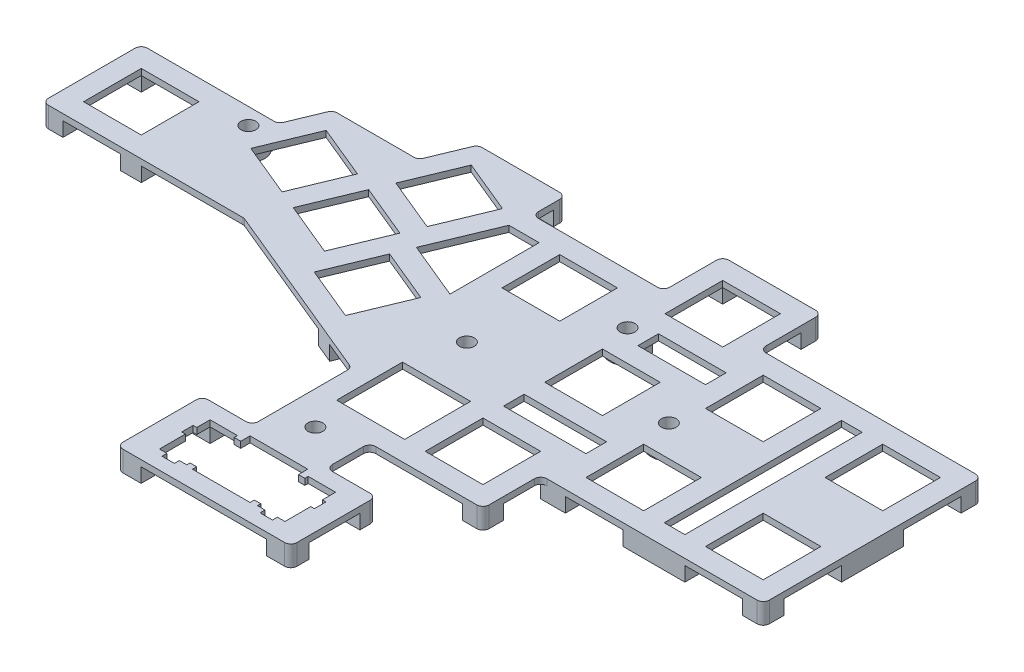
SolidWorks part; units mm, degrees
ref_plane "Front Plane" through (0, 0, 0) normal (0, 0, 1) x (1, 0, 0)
ref_plane "Top Plane" through (0, 0, 0) normal (0, 1, 0) x (1, 0, 0)
ref_plane "Right Plane" through (0, 0, 0) normal (1, 0, 0) x (0, 0, -1)
sketch "Button Reference" plane through (0, 0, 0) normal (0, 1, 0) x (1, 0, 0)
  line L0 (24.5, 61) -> (24.5, 32) construction
  line L1 (-36.2591, 48.1292) -> (-29.3708, 64.7591) construction
  line L2 (49.5, 75) -> (49.5, 46) construction
  line L3 (78.5, 75) -> (78.5, 46) construction
  line L4 (17.5, 0) -> (-17.5, 0) construction
  line L5 (-36.2591, 48.1292) -> (-19.6292, 41.2409) construction
  line L6 (17.5, -12.5) -> (-17.5, -12.5)
  line L7 (17.5, 12.5) -> (-17.5, 12.5)
  line L8 (24.6803, 89.9994) -> (49.5, 75) construction
  line L9 (24.6803, 89.9994) -> (24.5, 61) construction
  line L10 (-0.5241, 75.6559) -> (24.6803, 89.9994) construction
  line L11 (-0.5241, 75.6559) -> (24.5, 61) construction
  line L12 (-29.3708, 64.7591) -> (-12.7409, 57.8708) construction
  line L13 (-19.6292, 41.2409) -> (-12.7409, 57.8708) construction
  line L14 (-36.2591, 48.1292) -> (-12.7409, 57.8708) construction
  line L15 (-29.3708, 64.7591) -> (-19.6292, 41.2409) construction
  line L16 (-35.6984, 52.2266) -> (-28.8101, 68.8564) construction
  line L17 (-35.6984, 52.2266) -> (-52.3282, 59.1149) construction
  line L18 (-28.8101, 68.8564) -> (-45.4399, 75.7447) construction
  line L19 (-52.3282, 59.1149) -> (-45.4399, 75.7447) construction
  line L20 (-35.6984, 52.2266) -> (-45.4399, 75.7447) construction
  line L21 (-28.8101, 68.8564) -> (-52.3282, 59.1149) construction
  line L22 (-69.9281, 66.405) -> (-63.0398, 83.0348) construction
  line L23 (-69.9281, 66.405) -> (-53.2983, 59.5167) construction
  line L24 (-63.0398, 83.0348) -> (-46.41, 76.1465) construction
  line L25 (-53.2983, 59.5167) -> (-46.41, 76.1465) construction
  line L26 (-69.9281, 66.405) -> (-46.41, 76.1465) construction
  line L27 (-63.0398, 83.0348) -> (-53.2983, 59.5167) construction
  line L28 (-40.5692, 63.9856) -> (-22.9693, 56.6955) construction
  line L29 (-40.5692, 63.9856) -> (-58.1691, 71.2758) construction
  line L30 (-45.0381, 76.7148) -> (-38.1498, 93.3446) construction
  line L31 (-45.0381, 76.7148) -> (-28.4083, 69.8265) construction
  line L32 (-38.1498, 93.3446) -> (-21.52, 86.4563) construction
  line L33 (-28.4083, 69.8265) -> (-21.52, 86.4563) construction
  line L34 (-45.0381, 76.7148) -> (-21.52, 86.4563) construction
  line L35 (-38.1498, 93.3446) -> (-28.4083, 69.8265) construction
  line L36 (-40.5692, 63.9856) -> (-33.2791, 81.5855) construction
  line L37 (-24.5, 53) -> (-22.9693, 56.6955) construction
  line L38 (-58.1691, 71.2758) -> (-65.4592, 53.6759) construction
  line L39 (-65.4592, 53.6759) -> (-90.4039, 64.0083) construction
  line L40 (-70.5814, 66.1344) -> (-63.3104, 83.6881)
  line L41 (-63.3104, 83.6881) -> (-45.7105, 76.398)
  line L42 (-45.7105, 76.398) -> (-38.4204, 93.9979)
  line L43 (-38.4204, 93.9979) -> (-20.8667, 86.7269)
  line L44 (-20.8667, 86.7269) -> (-29.6876, 65.4315)
  line L45 (-29.6876, 65.4315) -> (-12.0877, 58.1414)
  line L46 (-12.0877, 58.1414) -> (-19.3586, 40.5877)
  line L47 (-19.3586, 40.5877) -> (-36.9123, 47.8586)
  line L48 (-36.9123, 47.8586) -> (-35.3816, 51.5542)
  line L49 (-35.3816, 51.5542) -> (-70.5814, 66.1344)
  line L50 (-66.484, 74.7199) -> (-66.9459, 74.9112) construction
  line L51 (-29.6436, 90.3624) -> (-29.8349, 89.9005) construction
  line L52 (-16.1851, 49.5558) -> (-15.7231, 49.3645) construction
  line L53 (-33.2791, 81.8539) -> (-33.2791, 81.5855) construction
  line L54 (46.566, 100.92) -> (46.566, 75) construction
  line L55 (46.566, 75) -> (49.5, 75) construction
  circle A0 centre (24.5, 32) radius 12.5
  circle A1 centre (24.5, 61) radius 12.5
  circle A2 centre (49.5, 46) radius 12.5
  circle A3 centre (49.5, 75) radius 12.5
  circle A4 centre (78.5, 75) radius 12.5
  circle A5 centre (78.5, 46) radius 12.5
  arc A6 (17.5, -12.5) -> (17.5, 12.5) centre (17.5, 0) ccw
  arc A7 (-17.5, 12.5) -> (-17.5, -12.5) centre (-17.5, 0) ccw
  circle A8 centre (-90.4039, 64.0083) radius 15.5
  circle A9 centre (24.6803, 89.9994) radius 12.5
  circle A10 centre (-0.5241, 75.6559) radius 12.5
  circle A11 centre (46.566, 100.92) radius 2.8
  circle A12 centre (62.066, 100.92) radius 2.8
  circle A13 centre (77.566, 100.92) radius 2.8
  circle A14 centre (93.066, 100.92) radius 2.8
  point P1 (-24.5, 53)
  point P3 (-40.5692, 63.9856)
  point P4 (-58.1691, 71.2758)
  point P35 (0, 0)
  point P43 (-33.2791, 81.5855)
  point P50 (-30, 0)
  point P51 (30, 0)
  dimension "D2" = 25
  dimension "D6" = 12.5
  dimension "D10" = 31
  dimension "D26" = 5.6
  dimension "D1" = 29
  dimension "D3" = 25
  dimension "D4" = 29
  dimension "D5" = 14
  dimension "D7" = 32
  dimension "D8" = 7
  dimension "D9" = 60
  dimension "D11" = 29
  dimension "D12" = 29
  dimension "D13" = 7
  dimension "D14" = 18
  dimension "D15" = 27
  dimension "D16" = 19.05
  dimension "D17" = 19.05
  dimension "D18" = 53
  dimension "D19" = 4
  dimension "D20" = 0.5
  dimension "D21" = 0.5
  dimension "D22" = 0.5
  dimension "D23" = 0.5
  dimension "D24" = 0.5
  dimension "D25" = 22.5
  dimension "D27" = 15.5
  dimension "D28" = 15.5
  dimension "D29" = 15.5
  dimension "D30" = 25.92
  dimension "D31" = 2.934
sketch "Sketch2" plane through (0, 0, 0) normal (0, 1, 0) x (1, 0, 0)
  line L0 (90.5, 34) -> (90.5, 87)
  line L1 (-97.4039, 57.0083) -> (-83.4039, 57.0083)
  line L2 (-97.4039, 57.0083) -> (-97.4039, 71.0083)
  line L3 (-97.4039, 71.0083) -> (-83.4039, 71.0083)
  line L4 (-83.4039, 57.0083) -> (-83.4039, 71.0083)
  line L5 (-97.4039, 57.0083) -> (-83.4039, 71.0083) construction
  line L6 (-97.4039, 71.0083) -> (-83.4039, 57.0083) construction
  line L11 (-67.315, 67.4874) -> (-61.9574, 80.4217)
  line L12 (-67.315, 67.4874) -> (-54.3807, 62.1298)
  line L17 (-61.9574, 80.4217) -> (-49.0231, 75.0641)
  line L18 (-54.3807, 62.1298) -> (-49.0231, 75.0641)
  line L23 (-67.315, 67.4874) -> (-49.0231, 75.0641) construction
  line L24 (-61.9574, 80.4217) -> (-54.3807, 62.1298) construction
  line L30 (-31.4232, 67.774) -> (-44.3575, 73.1316)
  line L31 (-31.4232, 67.774) -> (-36.7808, 54.8397)
  line L33 (-7.5241, 68.6559) -> (6.4759, 68.6559)
  line L34 (-7.5241, 68.6559) -> (-7.5241, 82.6559)
  line L35 (-7.5241, 82.6559) -> (6.4759, 82.6559)
  line L36 (6.4759, 68.6559) -> (6.4759, 82.6559)
  line L37 (-7.5241, 68.6559) -> (6.4759, 82.6559) construction
  line L38 (-7.5241, 82.6559) -> (6.4759, 68.6559) construction
  line L39 (17.6803, 82.9994) -> (31.6803, 82.9994)
  line L40 (17.6803, 82.9994) -> (17.6803, 96.9994)
  line L41 (17.6803, 96.9994) -> (31.6803, 96.9994)
  line L42 (31.6803, 82.9994) -> (31.6803, 96.9994)
  line L43 (17.6803, 82.9994) -> (31.6803, 96.9994) construction
  line L44 (17.6803, 96.9994) -> (31.6803, 82.9994) construction
  line L45 (17.5, 68) -> (31.5, 68)
  line L46 (17.5, 68) -> (17.5, 54)
  line L47 (17.5, 54) -> (31.5, 54)
  line L48 (31.5, 68) -> (31.5, 54)
  line L49 (17.5, 68) -> (31.5, 54) construction
  line L50 (17.5, 54) -> (31.5, 68) construction
  line L51 (17.5, 39) -> (31.5, 39)
  line L52 (17.5, 39) -> (17.5, 25)
  line L53 (17.5, 25) -> (31.5, 25)
  line L54 (31.5, 39) -> (31.5, 25)
  line L55 (17.5, 39) -> (31.5, 25) construction
  line L56 (17.5, 25) -> (31.5, 39) construction
  line L57 (42.5, 39) -> (56.5, 39)
  line L58 (42.5, 39) -> (42.5, 53)
  line L59 (42.5, 53) -> (56.5, 53)
  line L60 (56.5, 39) -> (56.5, 53)
  line L61 (42.5, 39) -> (56.5, 53) construction
  line L62 (42.5, 53) -> (56.5, 39) construction
  line L63 (42.5, 82) -> (56.5, 82)
  line L64 (42.5, 82) -> (42.5, 68)
  line L65 (42.5, 68) -> (56.5, 68)
  line L66 (56.5, 82) -> (56.5, 68)
  line L67 (42.5, 82) -> (56.5, 68) construction
  line L68 (42.5, 68) -> (56.5, 82) construction
  line L69 (71.5, 68) -> (85.5, 68)
  line L70 (71.5, 68) -> (71.5, 82)
  line L71 (71.5, 82) -> (85.5, 82)
  line L72 (85.5, 68) -> (85.5, 82)
  line L73 (71.5, 68) -> (85.5, 82) construction
  line L74 (71.5, 82) -> (85.5, 68) construction
  line L75 (71.5, 39) -> (85.5, 39)
  line L76 (71.5, 39) -> (71.5, 53)
  line L77 (71.5, 53) -> (85.5, 53)
  line L78 (85.5, 39) -> (85.5, 53)
  line L79 (71.5, 39) -> (85.5, 53) construction
  line L80 (71.5, 53) -> (85.5, 39) construction
  line L85 (7, 4.73) -> (8.575, 4.73)
  line L88 (-44.3575, 73.1316) -> (-49.7151, 60.1973)
  line L89 (-36.7808, 54.8397) -> (-49.7151, 60.1973)
  line L90 (-31.4232, 67.774) -> (-49.7151, 60.1973) construction
  line L91 (-44.3575, 73.1316) -> (-36.7808, 54.8397) construction
  line L92 (-33.6459, 49.2116) -> (-20.7116, 43.8541)
  line L93 (-33.6459, 49.2116) -> (-28.2884, 62.1459)
  line L94 (-20.7116, 43.8541) -> (-15.3541, 56.7884)
  line L95 (-28.2884, 62.1459) -> (-15.3541, 56.7884)
  line L96 (-33.6459, 49.2116) -> (-15.3541, 56.7884) construction
  line L97 (-20.7116, 43.8541) -> (-28.2884, 62.1459) construction
  line L98 (-42.425, 77.7972) -> (-37.0674, 90.7315)
  line L99 (-42.425, 77.7972) -> (-29.4907, 72.4396)
  line L100 (-37.0674, 90.7315) -> (-24.1331, 85.3739)
  line L101 (-29.4907, 72.4396) -> (-24.1331, 85.3739)
  line L102 (-42.425, 77.7972) -> (-24.1331, 85.3739) construction
  line L103 (-37.0674, 90.7315) -> (-29.4907, 72.4396) construction
  line L104 (-28.8101, 68.8564) -> (-45.4399, 75.7447) construction
  line L106 (90.5, 87) -> (36.6803, 87)
  line L107 (36.6803, 87) -> (36.6803, 101.9994)
  line L128 (21.1, -11.22) -> (-21.1, -11.22)
  line L129 (-102.4039, 76.0083) -> (-102.4039, 52.0083)
  line L131 (90.5, 34) -> (36.5, 34)
  line L132 (36.5, 34) -> (36.5, 20)
  line L133 (36.5, 20) -> (9, 20)
  line L134 (9, 20) -> (9, 9.5)
  line L137 (36.6803, 101.9994) -> (12.6803, 101.9994)
  line L138 (-40.4083, 95.7315) -> (-44.6788, 85.4217)
  line L139 (-44.6788, 85.4217) -> (-65.2983, 85.4217)
  line L140 (-65.2983, 85.4217) -> (-69.1975, 76.0083)
  line L141 (-69.1975, 76.0083) -> (-102.4039, 76.0083)
  line L142 (-9, 9.5) -> (-9, 33.591)
  line L143 (-9, 33.591) -> (-53.4633, 52.0083)
  line L144 (-53.4633, 52.0083) -> (-102.4039, 52.0083)
  line L145 (-40.4083, 95.7315) -> (-19.1331, 95.7315)
  line L146 (12.6803, 95.7315) -> (12.6803, 101.9994)
  line L150 (-9, 9.5) -> (-21.1, 9.5)
  line L151 (-21.1, -11.22) -> (-21.1, 9.5)
  line L154 (9, 9.5) -> (21.1, 9.5)
  line L155 (21.1, -11.22) -> (21.1, 9.5)
  line L171 (-7, 7) -> (7, 7)
  line L174 (7, -7) -> (7, -5.97)
  line L175 (9, 9.5) -> (-9, 9.5) construction
  line L176 (0, 7) -> (0, -7) construction
  line L185 (-7, -7) -> (7, -7)
  line L186 (8.575, 4.73) -> (8.575, 5.53)
  line L187 (8.575, 5.53) -> (15.225, 5.53)
  line L188 (15.225, 5.53) -> (15.225, 2.3)
  line L189 (15.225, 2.3) -> (16.1, 2.3)
  line L190 (16.1, 2.3) -> (16.1, -0.5)
  line L191 (16.1, -0.5) -> (15.225, -0.5)
  line L192 (15.225, -0.5) -> (15.225, -6.77)
  line L193 (15.225, -6.77) -> (13.4, -6.77)
  line L194 (13.4, -6.77) -> (13.4, -7.97)
  line L195 (13.4, -7.97) -> (10.4, -7.97)
  line L196 (10.4, -7.97) -> (10.4, -6.77)
  line L197 (10.4, -6.77) -> (8.575, -6.77)
  line L198 (8.575, -6.77) -> (8.575, -5.97)
  line L199 (8.575, -5.97) -> (7, -5.97)
  line L200 (11.938, 5.492) -> (11.938, -7.97) construction
  line L201 (-16.1, 0) -> (16.1, 0) construction
  line L202 (7, 4.73) -> (7, 7)
  line L203 (-8.575, 4.73) -> (-8.575, 5.53)
  line L204 (-8.575, -6.77) -> (-8.575, -5.97)
  line L205 (-7, -7) -> (-7, -5.97)
  line L206 (-8.575, -5.97) -> (-7, -5.97)
  line L207 (-10.4, -6.77) -> (-8.575, -6.77)
  line L208 (-10.4, -7.97) -> (-10.4, -6.77)
  line L209 (-13.4, -6.77) -> (-13.4, -7.97)
  line L210 (-13.4, -7.97) -> (-10.4, -7.97)
  line L211 (-11.938, 5.492) -> (-11.938, -7.97) construction
  line L212 (-15.225, -6.77) -> (-13.4, -6.77)
  line L213 (-15.225, -0.5) -> (-15.225, -6.77)
  line L214 (-16.1, -0.5) -> (-15.225, -0.5)
  line L215 (-16.1, 2.3) -> (-16.1, -0.5)
  line L216 (-15.225, 2.3) -> (-16.1, 2.3)
  line L217 (-15.225, 5.53) -> (-15.225, 2.3)
  line L218 (-8.575, 5.53) -> (-15.225, 5.53)
  line L219 (-7, 4.73) -> (-8.575, 4.73)
  line L220 (-7, 4.73) -> (-7, 7)
  line L221 (12.6803, 95.7315) -> (12.6803, 87.6559)
  line L222 (12.6803, 87.6559) -> (-19.1331, 87.6559)
  line L223 (-19.1331, 87.6559) -> (-19.1331, 95.7315)
  point P0 (-90.4039, 64.0083)
  point P7 (-58.1691, 71.2758)
  point P8 (-40.5692, 63.9856)
  point P9 (-24.5, 53)
  point P15 (-33.2791, 81.5855)
  point P32 (-0.5241, 75.6559)
  point P38 (24.6803, 89.9994)
  point P44 (24.5, 61)
  point P50 (24.5, 32)
  point P56 (49.5, 46)
  point P62 (49.5, 75)
  point P68 (78.5, 75)
  point P74 (78.5, 46)
  point P80 (0, 0)
  point P81 (0, 0)
  point P159 (0, 9.5)
  point P174 (0, 0)
  dimension "D2" = 5
  dimension "D3" = 14
  dimension "D5" = 5
  dimension "D6" = 5
  dimension "D7" = 5
  dimension "D8" = 5
  dimension "D9" = 5
  dimension "D10" = 14
  dimension "D11" = 5
  dimension "D12" = 5
  dimension "D13" = 5
  dimension "D14" = 5
  dimension "D15" = 5
  dimension "D16" = 5
  dimension "D18" = 5
  dimension "D19" = 5
  dimension "D20" = 17.15
  dimension "D21" = 5
  dimension "D22" = 5
  dimension "D23" = 30.45
  dimension "D24" = 32.2
  dimension "D25" = 18
  dimension "D27" = 4.73
  dimension "D28" = 2.3
  dimension "D29" = 0.5
  dimension "D30" = 7.97
  dimension "D31" = 6.77
  dimension "D32" = 5.97
  dimension "D33" = 23.876
  dimension "D26" = 5.53
  dimension "D34" = 20.8
  dimension "D35" = 26.8
  dimension "D36" = 5
  dimension "D37" = 5
  dimension "D38" = 2.5
  dimension "D39" = 3.25
  dimension "D40" = 5
  dimension "D41" = 5
extrude "Key Plate" add sketch "Sketch2" along normal blind 1.5
sketch "Sketch3" plane through (0, 0, 0) normal (0, -1, 0) x (1, 0, 0)
  line L0 (-20.7116, -43.8541) -> (-22.625, -39.2347)
  line L13 (90.5, -34) -> (85.5, -34)
  line L14 (90.5, -34) -> (90.5, -39)
  line L15 (90.5, -39) -> (85.5, -39)
  line L16 (85.5, -34) -> (85.5, -39)
  line L17 (36.5, -20) -> (31.5, -20)
  line L18 (36.5, -20) -> (36.5, -25)
  line L19 (36.5, -25) -> (31.5, -25)
  line L20 (31.5, -20) -> (31.5, -25)
  line L29 (-102.4039, -52.0083) -> (-97.4039, -52.0083)
  line L30 (-102.4039, -52.0083) -> (-102.4039, -57.0083)
  line L31 (-102.4039, -57.0083) -> (-97.4039, -57.0083)
  line L32 (-97.4039, -52.0083) -> (-97.4039, -57.0083)
  line L33 (-97.4039, -71.0083) -> (-102.4039, -71.0083)
  line L34 (-97.4039, -71.0083) -> (-97.4039, -76.0083)
  line L35 (-97.4039, -76.0083) -> (-102.4039, -76.0083)
  line L36 (-102.4039, -71.0083) -> (-102.4039, -76.0083)
  line L37 (-20.7116, -43.8541) -> (-16.0922, -41.9406)
  line L38 (-22.625, -39.2347) -> (-18.0056, -37.3212)
  line L40 (-53.4633, -52.0083) -> (-9, -33.591) construction
  line L49 (-16.0922, -41.9406) -> (-18.0056, -37.3212)
  line L51 (-102.4039, -52.0083) -> (-53.4633, -52.0083) construction
  line L52 (-83.4039, -57.0083) -> (-78.4039, -57.0083)
  line L53 (-83.4039, -57.0083) -> (-83.4039, -52.0083)
  line L54 (-83.4039, -52.0083) -> (-78.4039, -52.0083)
  line L55 (-78.4039, -57.0083) -> (-78.4039, -52.0083)
  line L56 (-38.4204, -93.9979) -> (-20.8667, -86.7269) construction
  line L57 (17.6803, -96.9994) -> (12.6803, -96.9994)
  line L58 (36.5, -34) -> (90.5, -34) construction
  line L59 (-83.4039, -71.0083) -> (-76.2052, -71.0083)
  line L60 (-83.4039, -71.0083) -> (-83.4039, -76.0083)
  line L61 (-83.4039, -76.0083) -> (-69.1975, -76.0083)
  line L62 (-69.1975, -74.2697) -> (-69.1975, -76.0083)
  line L71 (36.5, -34) -> (42.5, -34)
  line L72 (36.5, -34) -> (36.5, -39)
  line L73 (36.5, -39) -> (42.5, -39)
  line L74 (42.5, -34) -> (42.5, -39)
  line L75 (56.5, -39) -> (71.5, -39)
  line L76 (56.5, -39) -> (56.5, -34)
  line L77 (56.5, -34) -> (71.5, -34)
  line L78 (71.5, -39) -> (71.5, -34)
  line L79 (90.5, -34) -> (90.5, -87) construction
  line L80 (85.5, -53) -> (90.5, -53)
  line L81 (85.5, -53) -> (85.5, -68)
  line L82 (85.5, -68) -> (90.5, -68)
  line L83 (90.5, -53) -> (90.5, -68)
  line L85 (36.6803, -101.9994) -> (31.6803, -101.9994)
  line L86 (36.6803, -101.9994) -> (36.6803, -96.9994)
  line L87 (36.6803, -96.9994) -> (31.6803, -96.9994)
  line L88 (31.6803, -101.9994) -> (31.6803, -96.9994)
  line L89 (85.5, -82) -> (90.5, -82)
  line L90 (85.5, -82) -> (85.5, -87)
  line L91 (85.5, -87) -> (90.5, -87)
  line L92 (90.5, -82) -> (90.5, -87)
  line L95 (-70.5814, -66.1344) -> (-63.3104, -83.6881) construction
  line L96 (17.5, -12.5) -> (-17.5, -12.5) construction
  line L97 (17.6803, -96.9994) -> (17.6803, -101.9994)
  line L98 (17.6803, -101.9994) -> (12.6803, -101.9994)
  line L99 (12.6803, -96.9994) -> (12.6803, -101.9994)
  line L100 (-19.1331, -95.7315) -> (-35.363, -95.7315)
  line L101 (-19.1331, -95.7315) -> (-19.1331, -92.7315)
  line L102 (-19.1331, -92.7315) -> (-35.363, -92.7315)
  line L103 (-35.363, -95.7315) -> (-35.363, -92.7315)
  line L105 (21.1, 11.22) -> (15.225, 11.22)
  line L106 (21.1, 11.22) -> (21.1, 6.77)
  line L107 (21.1, 6.77) -> (15.225, 6.77)
  line L108 (15.225, 11.22) -> (15.225, 6.77)
  line L109 (-21.1, 11.22) -> (-15.225, 11.22)
  line L110 (-21.1, 11.22) -> (-21.1, 6.77)
  line L111 (-21.1, 6.77) -> (-15.225, 6.77)
  line L112 (-15.225, 11.22) -> (-15.225, 6.77)
  line L113 (21.1, -9.5) -> (15.225, -9.5)
  line L114 (21.1, -9.5) -> (21.1, -5.53)
  line L115 (21.1, -5.53) -> (15.225, -5.53)
  line L116 (15.225, -9.5) -> (15.225, -5.53)
  line L117 (-21.1, -9.5) -> (-15.225, -9.5)
  line L118 (-21.1, -9.5) -> (-21.1, -5.53)
  line L119 (-21.1, -5.53) -> (-15.225, -5.53)
  line L120 (-15.225, -9.5) -> (-15.225, -5.53)
  circle A0 centre (-0.4039, -53) radius 4.25
  circle A1 centre (-0.9039, -16.75) radius 4.25
  circle A2 centre (41.0961, -60.5) radius 4.2594
  circle A3 centre (16.0961, -75.5) radius 4.2594
  arc A4 (-69.1975, -74.2697) -> (-76.2052, -71.0083) centre (-72.4039, -72) ccw
  circle A5 centre (24.5, -61) radius 12.5 construction
  circle A6 centre (49.5, -46) radius 12.5 construction
  point P0 (-72.4039, -72)
  dimension "D1" = 8.5
  dimension "D2" = 3
  dimension "D3" = 5
extrude "Feet" add sketch "Sketch3" along normal blind 3.5
hole_wizard "M3 Clearance Hole1" positions "3DSketch1" profile "Sketch5" hole size "M3" standard "ANSI Metric" end condition up to next
sketch3d "3DSketch1"
  line L0 (-0.4039, -3.5, -53) -> (-0.4039, 0, -53) construction
  line L1 (16.0961, -3.5, -75.5) -> (16.0961, 0, -75.5) construction
  line L2 (-0.9039, -3.5, -16.75) -> (-0.9039, 0, -16.75) construction
  line L3 (41.0961, -3.5, -60.5) -> (41.0961, 0, -60.5) construction
  line L4 (-72.4039, -3.5, -72) -> (-72.4039, 0, -72) construction
  point P0 (-0.4039, -3.5, -53)
  point P4 (41.0961, -3.5, -60.5)
  point P6 (16.0961, -3.5, -75.5)
  point P10 (-0.9039, -3.5, -16.75)
  point P18 (-72.4039, -3.5, -72)
sketch "Sketch5" plane through (-0.4039, -3.5, -53) normal (1, 0, 0) x (0, 0, -1)
  line L0 (0, 0) -> (0, 5)
  line L1 (0, 5) -> (1.8, 5)
  line L2 (1.8, 5) -> (1.8, 0.025)
  line L3 (1.8, 0.025) -> (1.825, 0)
  line L5 (1.825, 0) -> (0, 0)
  line L6 (-1.8, 0.025) -> (-1.825, 0) construction
  line L11 (0, -6.35) -> (0, 107.95) construction
  dimension "Thru Hole Dia." = 3.6
  dimension "Thru Hole Depth" = 5
  dimension "Near C'Sink Dia." = 3.65
  dimension "Near C'Sink Angle" = 90
fillet "Fillet1" radius 1.5 25 edges at (-21.1, -1, 11.22) (-21.1, -1, -9.5) (-9, 0.75, -9.5) (-9, 0.75, -33.591) (-53.4633, 0.75, -52.0083) (-102.4039, -1, -52.0083) (-102.4039, -1, -76.0083) (-69.1975, 0.75, -76.0083) (-65.2983, 0.75, -85.4217) (-44.6788, 0.75, -85.4217) (-40.4083, 0.75, -95.7315) (-19.1331, -1, -95.7315) (-19.1331, 0.75, -87.6559) (12.6803, 0.75, -87.6559) (12.6803, -1, -101.9994) (90.5, -1, -34) (36.5, 0.75, -34) (36.5, -1, -20) (9, 0.75, -20) (9, 0.75, -9.5) (21.1, -1, -9.5) (21.1, -1, 11.22) (36.6803, -1, -101.9994) (36.6803, 0.75, -87) (90.5, -1, -87)
sketch "Sketch6" plane through (0, 0, 0) normal (0, -1, 0) x (-1, 0, 0)
  line L0 (9, 32.5887) -> (9, 11) construction
  line L1 (4, 25) -> (-12.5, 25)
  line L2 (4, 25) -> (4, 41)
  line L3 (4, 41) -> (-12.5, 41)
  line L4 (-12.5, 25) -> (-12.5, 41)
  line L5 (-17.5, 39) -> (-17.5, 25) construction
  line L6 (-10.5, 20) -> (-31.5, 20) construction
  line L7 (-56.5, 39) -> (-56.5, 53) construction
  line L8 (-61.5, 39) -> (-66.5, 39)
  line L9 (-61.5, 39) -> (-61.5, 82)
  line L10 (-61.5, 82) -> (-66.5, 82)
  line L11 (-66.5, 39) -> (-66.5, 82)
  line L12 (-71.5, 53) -> (-71.5, 39) construction
  line L13 (-71.5, 34) -> (-56.5, 34) construction
  line L14 (-85.5, 87) -> (-38.1803, 87) construction
  line L15 (12.5241, 61.0281) -> (26.4211, 66.7845)
  line L16 (26.4211, 66.7845) -> (19.847, 82.6559)
  line L17 (19.847, 82.6559) -> (12.5241, 82.6559)
  line L18 (12.5241, 82.6559) -> (12.5241, 61.0281)
  line L19 (15.3541, 56.7884) -> (28.2884, 62.1459) construction
  line L20 (29.4907, 72.4396) -> (24.1331, 85.3739) construction
  line L21 (-11.1803, 87.6559) -> (17.6331, 87.6559) construction
  line L22 (7.5241, 82.6559) -> (7.5241, 68.6559) construction
  line L23 (-42.5, 53) -> (-42.5, 39) construction
  line L24 (-37.5, 49) -> (-17.5, 49)
  line L25 (-37.5, 49) -> (-37.5, 44)
  line L26 (-37.5, 44) -> (-17.5, 44)
  line L27 (-17.5, 49) -> (-17.5, 44)
  line L28 (-17.5, 54) -> (-31.5, 54) construction
  line L29 (-31.5, 39) -> (-17.5, 39) construction
  line L30 (-42.5, 82) -> (-42.5, 68) construction
  line L31 (-37.5, 77.9994) -> (-21.0961, 77.9994)
  line L32 (-37.5, 77.9994) -> (-37.5, 73)
  line L33 (-37.5, 73) -> (-21.0961, 73)
  line L34 (-21.0961, 77.9994) -> (-21.0961, 73)
  line L35 (-17.6803, 82.9994) -> (-31.6803, 82.9994) construction
  line L36 (-31.5, 68) -> (-17.5, 68) construction
  circle A1 centre (0.4039, 53) radius 4.25 construction
  circle A2 centre (-16.0961, 75.5) radius 4.2594 construction
  point P46 (-17.5, 46.5)
  dimension "D1" = 5
  dimension "D2" = 5
  dimension "D3" = 5
  dimension "D4" = 12
  dimension "D5" = 5
  dimension "D6" = 5
  dimension "D7" = 5
  dimension "D8" = 5
  dimension "D9" = 5
  dimension "D10" = 5
  dimension "D11" = 5
  dimension "D12" = 5
  dimension "D13" = 5
  dimension "D14" = 5
  dimension "D15" = 5
  dimension "D16" = 5
  dimension "D17" = 5
  dimension "D18" = 5
  dimension "D19" = 5
  dimension "D20" = 5
extrude "Cut-Extrude1" cut sketch "Sketch6" against normal blind 10
